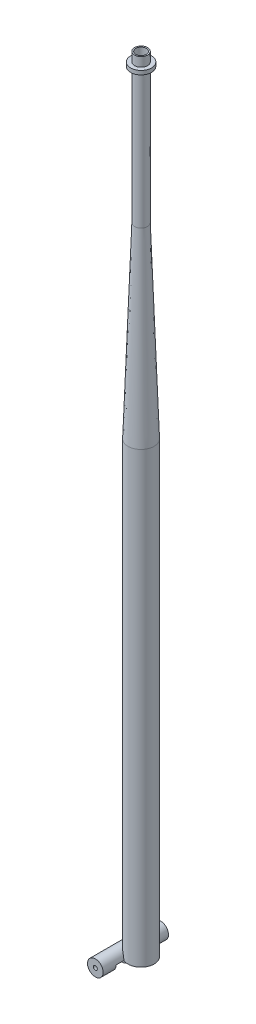
SolidWorks part; units mm, degrees
ref_plane "Plan de face" through (0, 0, 0) normal (0, 0, 1) x (1, 0, 0)
ref_plane "Plan de dessus" through (0, 0, 0) normal (0, 1, 0) x (1, 0, 0)
ref_plane "Plan de droite" through (0, 0, 0) normal (1, 0, 0) x (0, 0, -1)
sketch "Esquisse1" plane through (0, 0, 0) normal (0, 1, 0) x (1, 0, 0)
  circle A0 centre (0, 0) radius 5
  dimension "D1" = 10
extrude "Boss.-Extru.1" add sketch "Esquisse1" along normal blind 600
sketch "Esquisse2" plane through (0, 0, 0) normal (0, 1, 0) x (1, 0, 0)
  circle A0 centre (0, 0) radius 10
  dimension "D1" = 20
extrude "Boss.-Extru.2" add sketch "Esquisse2" along normal blind 200
chamfer "Chanfrein1" distance 10 angle 88 1 edges at (0, 200, 5) first distance on face at (0, 200, 5)
sketch "Esquisse3" plane through (0, 600, 0) normal (0, 1, 0) x (1, 0, 0)
  circle A0 centre (0, 0) radius 4
  dimension "D1" = 8
extrude "Enlèv. mat.-Extru.1" cut sketch "Esquisse3" against normal through all
sketch3d "Esquisse3D1" plane through (0, 0, 0) normal (0, 0, 1) x (1, 0, 0)
  dimension "D1" = 10
sketch "Esquisse4" plane through (0, 590, 0) normal (0, 1, 0) x (1, 0, 0)
  circle A0 centre (0, 0) radius 8
  circle A1 centre (0, 0) radius 4.5
  circle A2 centre (0, 0) radius 5 construction
  dimension "D1" = 9
  dimension "D2" = 3
extrude "Boss.-Extru.3" add sketch "Esquisse4" along normal blind 3
sketch "Esquisse5" plane through (0, 0, 0) normal (0, 0, 1) x (1, 0, 0)
  line L0 (-10, 343.1813) -> (-10, 0) construction
  line L1 (-10, 0) -> (10, 0) construction
  circle A0 centre (-10, 0) radius 6
extrude "Boss.-Extru.4" add sketch "Esquisse5" along normal mid plane 50
sketch "Esquisse6" plane through (0, 0, 0) normal (1, 0, 0) x (0, 0, -1)
  line L0 (9.1652, 0) -> (0, 0) construction
  line L19 (-5, 0) -> (5, 0) construction
  line L20 (-15, 0) -> (-5, 0)
  line L21 (-15, 0) -> (-15, -13.3403)
  line L22 (-15, -13.3403) -> (-5, -13.3403)
  line L23 (-5, 0) -> (-5, -13.3403)
  line L24 (5, -13.3403) -> (15, -13.3403)
  line L25 (5, -13.3403) -> (5, 0)
  line L26 (5, 0) -> (15, 0)
  line L27 (15, -13.3403) -> (15, 0)
  dimension "D1" = 10
  dimension "D2" = 10
  dimension "D3" = 10
extrude "Enlèv. mat.-Extru.2" cut sketch "Esquisse6" against normal through all both and the other way through all
sketch "Esquisse7" plane through (0, 0, 25) normal (0, 0, 1) x (1, 0, 0)
  circle A0 centre (-10, 0) radius 1.5
  circle A1 centre (-10, 0) radius 6 construction
  dimension "D1" = 3
extrude "Enlèv. mat.-Extru.3" cut sketch "Esquisse7" against normal through all
